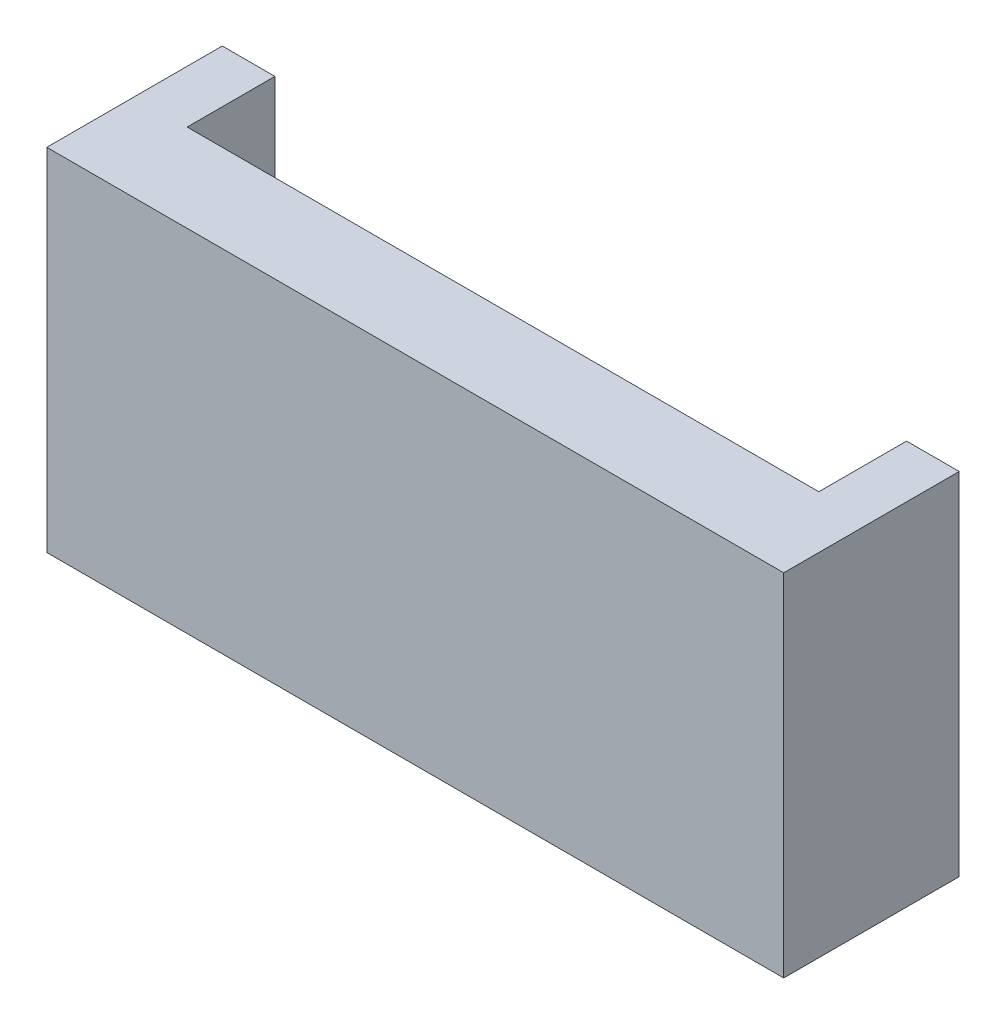
SolidWorks part; units mm, degrees
ref_plane "Front Plane" through (0, 0, 0) normal (0, 0, 1) x (1, 0, 0)
ref_plane "Top Plane" through (0, 0, 0) normal (0, 1, 0) x (1, 0, 0)
ref_plane "Right Plane" through (0, 0, 0) normal (1, 0, 0) x (0, 0, -1)
sketch "Sketch1" plane through (0, 0, 0) normal (0, 1, 0) x (1, 0, 0)
  line L1 (-5.8482, 2.6116) -> (12.1518, 2.6116)
  line L2 (-5.8482, 2.6116) -> (-5.8482, -2.3884)
  line L3 (-5.8482, -2.3884) -> (12.1518, -2.3884)
  line L4 (12.1518, 2.6116) -> (12.1518, -2.3884)
  dimension "D1" = 5
  dimension "D2" = 18
extrude "Boss-Extrude1" add sketch "Sketch1" along normal blind 1.5
sketch "Sketch2" plane through (0, 1.5, 0) normal (0, 1, 0) x (1, 0, 0)
  line L1 (12.1518, -2.3884) -> (12.1518, 2.6116) construction
  line L2 (-5.8482, -2.3884) -> (12.1518, -2.3884)
  line L3 (-5.8482, -2.3884) -> (-5.8482, 0.1116)
  line L4 (-5.8482, 0.1116) -> (12.1518, 0.1116)
  line L5 (12.1518, -2.3884) -> (12.1518, 0.1116)
  line L6 (-5.8482, 0.1116) -> (-5.8482, 1.6116) construction
  line L7 (-5.8482, 2.6116) -> (-5.8482, -2.3884) construction
  line L8 (12.1518, 2.6116) -> (-5.8482, 2.6116) construction
  line L9 (-5.8482, 1.6116) -> (-0.8482, 1.6116)
  line L10 (-5.8482, 1.6116) -> (-5.8482, 2.6116)
  line L11 (-5.8482, 2.6116) -> (-0.8482, 2.6116)
  line L12 (-0.8482, 1.6116) -> (-0.8482, 2.6116)
  line L14 (12.1518, 1.6116) -> (7.3518, 1.6116)
  line L15 (12.1518, 1.6116) -> (12.1518, 2.6116)
  line L16 (12.1518, 2.6116) -> (7.3518, 2.6116)
  line L17 (7.3518, 1.6116) -> (7.3518, 2.6116)
  dimension "D1" = 2.5
  dimension "D2" = 5
  dimension "D3" = 4.8
  dimension "D4" = 1
  dimension "D5" = 1
extrude "Boss-Extrude3" add sketch "Sketch2" along normal blind 4.5
sketch "Sketch4" plane through (0, 6, 0) normal (0, 1, 0) x (1, 0, 0)
  line L1 (12.1518, -2.3884) -> (-5.8482, -2.3884)
  line L2 (12.1518, -2.3884) -> (12.1518, 0.1116)
  line L3 (12.1518, 0.1116) -> (-5.8482, 0.1116)
  line L4 (-5.8482, -2.3884) -> (-5.8482, 0.1116)
extrude "Boss-Extrude4" add sketch "Sketch4" along normal blind 4
sketch "Sketch6" plane through (12.1518, 0, 0) normal (1, 0, 0) x (0, 0, -1)
  line L1 (-2.3884, 0) -> (2.6116, 0)
  line L2 (-2.3884, 0) -> (-2.3884, 10)
  line L3 (-2.3884, 10) -> (2.6116, 10)
  line L4 (2.6116, 0) -> (2.6116, 10)
  dimension "D1" = 10
  dimension "D2" = 5
extrude "Boss-Extrude5" add sketch "Sketch6" along normal blind 1.5
sketch "Sketch7" plane through (-5.8482, 0, 0) normal (-1, 0, 0) x (0, 0, 1)
  line L1 (2.3884, 0) -> (-2.6116, 0)
  line L2 (2.3884, 0) -> (2.3884, 10)
  line L3 (2.3884, 10) -> (-2.6116, 10)
  line L4 (-2.6116, 0) -> (-2.6116, 10)
extrude "Boss-Extrude6" add sketch "Sketch7" along normal blind 1.5
